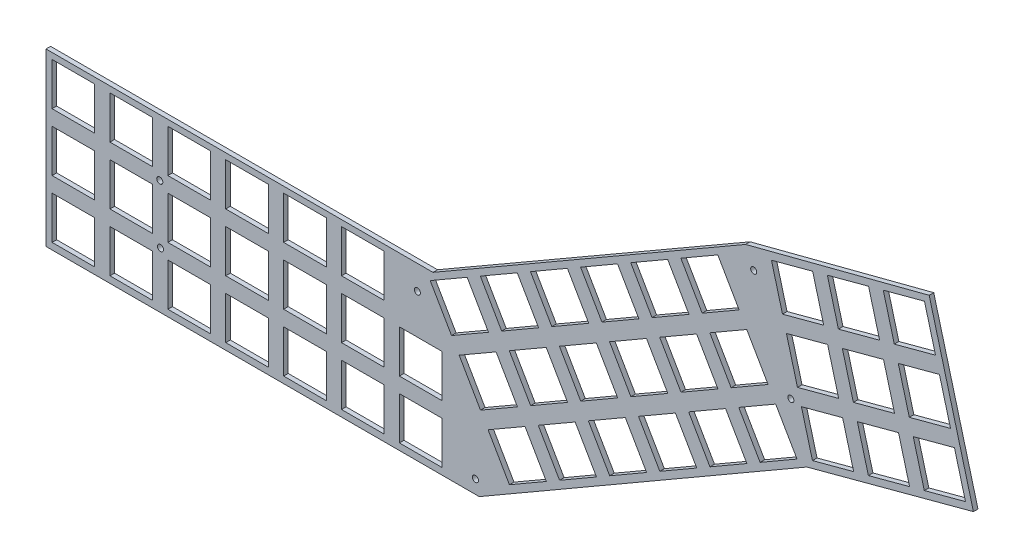
SolidWorks part; units mm, degrees
ref_plane "Plan de face" through (0, 0, 0) normal (0, 0, 1) x (1, 0, 0)
ref_plane "Plan de dessus" through (0, 0, 0) normal (0, 1, 0) x (1, 0, 0)
ref_plane "Plan de droite" through (0, 0, 0) normal (1, 0, 0) x (0, 0, -1)
sketch "Model" plane through (0, 0, 0) normal (0, 0, 1) x (1, 0, 0)
  line L0 (152.8114, 25.9717) -> (138.2826, 80.2215)
  line L1 (98.1506, 11.3316) -> (152.8114, 25.9717)
  line L2 (-9.3986, -50.8585) -> (98.1506, 11.3316)
  line L3 (-151.6088, -50.8585) -> (-9.3986, -50.8585)
  line L4 (-24.5886, 5.3017) -> (-151.6088, 5.2929)
  line L5 (78.0109, 64.5416) -> (-24.5886, 5.3017)
  line L6 (138.2826, 80.2215) -> (78.0109, 64.5416)
  line L7 (-151.6088, 5.3124) -> (-151.6088, -50.8585)
  line L8 (-54.6088, -34.6876) -> (-54.6088, -48.6876)
  line L9 (-54.6088, -48.6876) -> (-40.6088, -48.6876)
  line L10 (-40.6088, -34.6876) -> (-40.6088, -48.6876)
  line L11 (-54.6088, -34.6876) -> (-40.6088, -34.6876)
  line L12 (-35.6088, -34.6876) -> (-35.6088, -48.6876)
  line L13 (-35.6088, -48.6876) -> (-21.6088, -48.6876)
  line L14 (-21.6088, -34.6876) -> (-21.6088, -48.6876)
  line L15 (-35.6088, -34.6876) -> (-21.6088, -34.6876)
  line L16 (-35.6088, -15.6876) -> (-35.6088, -29.6876)
  line L17 (-35.6088, -29.6876) -> (-21.6088, -29.6876)
  line L18 (-21.6088, -15.6876) -> (-21.6088, -29.6876)
  line L19 (-35.6088, -15.6876) -> (-21.6088, -15.6876)
  line L20 (-54.6088, -15.6876) -> (-54.6088, -29.6876)
  line L21 (-54.6088, -29.6876) -> (-40.6088, -29.6876)
  line L22 (-40.6088, -15.6876) -> (-40.6088, -29.6876)
  line L23 (-54.6088, -15.6876) -> (-40.6088, -15.6876)
  line L24 (-54.6088, 3.3124) -> (-54.6088, -10.6876)
  line L25 (-54.6088, -10.6876) -> (-40.6088, -10.6876)
  line L26 (-40.6088, 3.3124) -> (-40.6088, -10.6876)
  line L27 (-54.6088, 3.3124) -> (-40.6088, 3.3124)
  line L28 (-73.6088, -34.6876) -> (-73.6088, -48.6876)
  line L29 (-73.6088, -48.6876) -> (-59.6088, -48.6876)
  line L30 (-59.6088, -34.6876) -> (-59.6088, -48.6876)
  line L31 (-73.6088, -34.6876) -> (-59.6088, -34.6876)
  line L32 (-73.6088, -15.6876) -> (-73.6088, -29.6876)
  line L33 (-73.6088, -29.6876) -> (-59.6088, -29.6876)
  line L34 (-59.6088, -15.6876) -> (-59.6088, -29.6876)
  line L35 (-73.6088, -15.6876) -> (-59.6088, -15.6876)
  line L36 (-73.6088, 3.3124) -> (-73.6088, -10.6876)
  line L37 (-73.6088, -10.6876) -> (-59.6088, -10.6876)
  line L38 (-59.6088, 3.3124) -> (-59.6088, -10.6876)
  line L39 (-73.6088, 3.3124) -> (-59.6088, 3.3124)
  line L40 (-92.6088, -34.6876) -> (-92.6088, -48.6876)
  line L41 (-92.6088, -48.6876) -> (-78.6088, -48.6876)
  line L42 (-78.6088, -34.6876) -> (-78.6088, -48.6876)
  line L43 (-92.6088, -34.6876) -> (-78.6088, -34.6876)
  line L44 (-92.6088, -15.6876) -> (-92.6088, -29.6876)
  line L45 (-92.6088, -29.6876) -> (-78.6088, -29.6876)
  line L46 (-78.6088, -15.6876) -> (-78.6088, -29.6876)
  line L47 (-92.6088, -15.6876) -> (-78.6088, -15.6876)
  line L48 (-92.6088, 3.3124) -> (-92.6088, -10.6876)
  line L49 (-92.6088, -10.6876) -> (-78.6088, -10.6876)
  line L50 (-78.6088, 3.3124) -> (-78.6088, -10.6876)
  line L51 (-92.6088, 3.3124) -> (-78.6088, 3.3124)
  line L52 (-111.6088, -34.6876) -> (-111.6088, -48.6876)
  line L53 (-111.6088, -48.6876) -> (-97.6088, -48.6876)
  line L54 (-97.6088, -34.6876) -> (-97.6088, -48.6876)
  line L55 (-111.6088, -34.6876) -> (-97.6088, -34.6876)
  line L56 (-111.6088, -15.6876) -> (-111.6088, -29.6876)
  line L57 (-111.6088, -29.6876) -> (-97.6088, -29.6876)
  line L58 (-97.6088, -15.6876) -> (-97.6088, -29.6876)
  line L59 (-111.6088, -15.6876) -> (-97.6088, -15.6876)
  line L60 (-130.6088, -34.6876) -> (-130.6088, -48.6876)
  line L61 (-130.6088, -48.6876) -> (-116.6088, -48.6876)
  line L62 (-116.6088, -34.6876) -> (-116.6088, -48.6876)
  line L63 (-130.6088, -34.6876) -> (-116.6088, -34.6876)
  line L64 (-130.6088, -15.6876) -> (-130.6088, -29.6876)
  line L65 (-130.6088, -29.6876) -> (-116.6088, -29.6876)
  line L66 (-116.6088, -15.6876) -> (-116.6088, -29.6876)
  line L67 (-130.6088, -15.6876) -> (-116.6088, -15.6876)
  line L68 (-149.6088, -34.6876) -> (-149.6088, -48.6876)
  line L69 (-149.6088, -48.6876) -> (-135.6088, -48.6876)
  line L70 (-135.6088, -34.6876) -> (-135.6088, -48.6876)
  line L71 (-149.6088, -34.6876) -> (-135.6088, -34.6876)
  line L72 (-149.6088, -15.6876) -> (-149.6088, -29.6876)
  line L73 (-149.6088, -29.6876) -> (-135.6088, -29.6876)
  line L74 (-135.6088, -15.6876) -> (-135.6088, -29.6876)
  line L75 (-149.6088, -15.6876) -> (-135.6088, -15.6876)
  line L76 (-111.6088, 3.3124) -> (-111.6088, -10.6876)
  line L77 (-111.6088, -10.6876) -> (-97.6088, -10.6876)
  line L78 (-97.6088, 3.3124) -> (-97.6088, -10.6876)
  line L79 (-111.6088, 3.3124) -> (-97.6088, 3.3124)
  line L80 (-130.6088, 3.3124) -> (-130.6088, -10.6876)
  line L81 (-130.6088, -10.6876) -> (-116.6088, -10.6876)
  line L82 (-116.6088, 3.3124) -> (-116.6088, -10.6876)
  line L83 (-130.6088, 3.3124) -> (-116.6088, 3.3124)
  line L84 (-149.6088, 3.3124) -> (-149.6088, -10.6876)
  line L85 (-149.6088, -10.6876) -> (-135.6088, -10.6876)
  line L86 (-135.6088, 3.3124) -> (-135.6088, -10.6876)
  line L87 (-149.6088, 3.3124) -> (-135.6088, 3.3124)
  line L88 (96.3487, 27.5969) -> (99.9722, 14.074)
  line L89 (99.9722, 14.074) -> (113.4951, 17.6974)
  line L90 (109.8717, 31.2204) -> (113.4951, 17.6974)
  line L91 (96.3487, 27.5969) -> (109.8717, 31.2204)
  line L92 (91.4311, 45.9495) -> (95.0546, 32.4266)
  line L93 (95.0546, 32.4266) -> (108.5776, 36.05)
  line L94 (104.9541, 49.573) -> (108.5776, 36.05)
  line L95 (91.4311, 45.9495) -> (104.9541, 49.573)
  line L96 (109.7837, 50.8671) -> (113.4072, 37.3441)
  line L97 (113.4072, 37.3441) -> (126.9302, 40.9676)
  line L98 (123.3067, 54.4906) -> (126.9302, 40.9676)
  line L99 (109.7837, 50.8671) -> (123.3067, 54.4906)
  line L100 (114.7013, 32.5145) -> (118.3248, 18.9915)
  line L101 (118.3248, 18.9915) -> (131.8477, 22.615)
  line L102 (128.2243, 36.138) -> (131.8477, 22.615)
  line L103 (114.7013, 32.5145) -> (128.2243, 36.138)
  line L104 (133.0539, 37.4321) -> (136.6774, 23.9091)
  line L105 (136.6774, 23.9091) -> (150.2003, 27.5326)
  line L106 (146.5768, 41.0555) -> (150.2003, 27.5326)
  line L107 (133.0539, 37.4321) -> (146.5768, 41.0555)
  line L108 (128.1363, 55.7847) -> (131.7598, 42.2617)
  line L109 (131.7598, 42.2617) -> (145.2828, 45.8852)
  line L110 (141.6593, 59.4081) -> (145.2828, 45.8852)
  line L111 (128.1363, 55.7847) -> (141.6593, 59.4081)
  line L112 (123.2188, 74.1372) -> (126.8422, 60.6143)
  line L113 (126.8422, 60.6143) -> (140.3652, 64.2378)
  line L114 (136.7417, 77.7607) -> (140.3652, 64.2378)
  line L115 (123.2188, 74.1372) -> (136.7417, 77.7607)
  line L116 (104.8662, 69.2197) -> (108.4896, 55.6967)
  line L117 (108.4896, 55.6967) -> (122.0126, 59.3202)
  line L118 (118.3891, 72.8432) -> (122.0126, 59.3202)
  line L119 (104.8662, 69.2197) -> (118.3891, 72.8432)
  line L120 (86.5136, 64.3021) -> (90.137, 50.7792)
  line L121 (90.137, 50.7792) -> (103.66, 54.4026)
  line L122 (100.0365, 67.9256) -> (103.66, 54.4026)
  line L123 (86.5136, 64.3021) -> (100.0365, 67.9256)
  line L124 (87.902, 24.0982) -> (94.902, 11.9739)
  line L125 (94.902, 11.9739) -> (82.7777, 4.9739)
  line L126 (75.7777, 17.0982) -> (82.7777, 4.9739)
  line L127 (87.902, 24.0982) -> (75.7777, 17.0982)
  line L128 (78.402, 40.5527) -> (85.402, 28.4283)
  line L129 (85.402, 28.4283) -> (73.2777, 21.4283)
  line L130 (66.2777, 33.5527) -> (73.2777, 21.4283)
  line L131 (78.402, 40.5527) -> (66.2777, 33.5527)
  line L132 (68.902, 57.0072) -> (75.902, 44.8828)
  line L133 (75.902, 44.8828) -> (63.7777, 37.8828)
  line L134 (56.7777, 50.0072) -> (63.7777, 37.8828)
  line L135 (68.902, 57.0072) -> (56.7777, 50.0072)
  line L136 (71.4475, 14.5982) -> (78.4475, 2.4739)
  line L137 (78.4475, 2.4739) -> (66.3232, -4.5261)
  line L138 (59.3232, 7.5982) -> (66.3232, -4.5261)
  line L139 (71.4475, 14.5982) -> (59.3232, 7.5982)
  line L140 (61.9475, 31.0527) -> (68.9475, 18.9283)
  line L141 (68.9475, 18.9283) -> (56.8232, 11.9283)
  line L142 (49.8232, 24.0527) -> (56.8232, 11.9283)
  line L143 (61.9475, 31.0527) -> (49.8232, 24.0527)
  line L144 (52.4475, 47.5072) -> (59.4475, 35.3828)
  line L145 (59.4475, 35.3828) -> (47.3232, 28.3828)
  line L146 (40.3232, 40.5072) -> (47.3232, 28.3828)
  line L147 (52.4475, 47.5072) -> (40.3232, 40.5072)
  line L148 (54.9931, 5.0982) -> (61.9931, -7.0261)
  line L149 (61.9931, -7.0261) -> (49.8687, -14.0261)
  line L150 (42.8687, -1.9018) -> (49.8687, -14.0261)
  line L151 (54.9931, 5.0982) -> (42.8687, -1.9018)
  line L152 (45.4931, 21.5527) -> (52.4931, 9.4283)
  line L153 (52.4931, 9.4283) -> (40.3687, 2.4283)
  line L154 (33.3687, 14.5527) -> (40.3687, 2.4283)
  line L155 (45.4931, 21.5527) -> (33.3687, 14.5527)
  line L156 (38.5386, -4.4018) -> (45.5386, -16.5261)
  line L157 (45.5386, -16.5261) -> (33.4142, -23.5261)
  line L158 (26.4142, -11.4018) -> (33.4142, -23.5261)
  line L159 (38.5386, -4.4018) -> (26.4142, -11.4018)
  line L160 (29.0386, 12.0527) -> (36.0386, -0.0717)
  line L161 (36.0386, -0.0717) -> (23.9142, -7.0717)
  line L162 (16.9142, 5.0527) -> (23.9142, -7.0717)
  line L163 (29.0386, 12.0527) -> (16.9142, 5.0527)
  line L164 (35.9931, 38.0072) -> (42.9931, 25.8828)
  line L165 (42.9931, 25.8828) -> (30.8687, 18.8828)
  line L166 (23.8687, 31.0072) -> (30.8687, 18.8828)
  line L167 (35.9931, 38.0072) -> (23.8687, 31.0072)
  line L168 (19.5386, 28.5072) -> (26.5386, 16.3828)
  line L169 (26.5386, 16.3828) -> (14.4142, 9.3828)
  line L170 (7.4142, 21.5072) -> (14.4142, 9.3828)
  line L171 (19.5386, 28.5072) -> (7.4142, 21.5072)
  line L172 (3.0841, 19.0072) -> (10.0841, 6.8828)
  line L173 (10.0841, 6.8828) -> (-2.0403, -0.1172)
  line L174 (-9.0403, 12.0072) -> (-2.0403, -0.1172)
  line L175 (3.0841, 19.0072) -> (-9.0403, 12.0072)
  line L176 (12.5841, 2.5527) -> (19.5841, -9.5717)
  line L177 (19.5841, -9.5717) -> (7.4597, -16.5717)
  line L178 (0.4597, -4.4473) -> (7.4597, -16.5717)
  line L179 (12.5841, 2.5527) -> (0.4597, -4.4473)
  line L180 (22.0841, -13.9018) -> (29.0841, -26.0261)
  line L181 (29.0841, -26.0261) -> (16.9597, -33.0261)
  line L182 (9.9597, -20.9018) -> (16.9597, -33.0261)
  line L183 (22.0841, -13.9018) -> (9.9597, -20.9018)
  line L184 (5.6296, -23.4018) -> (12.6296, -35.5261)
  line L185 (12.6296, -35.5261) -> (0.5053, -42.5261)
  line L186 (-6.4947, -30.4018) -> (0.5053, -42.5261)
  line L187 (5.6296, -23.4018) -> (-6.4947, -30.4018)
  line L188 (-3.8704, -6.9473) -> (3.1296, -19.0717)
  line L189 (3.1296, -19.0717) -> (-8.9947, -26.0717)
  line L190 (-15.9947, -13.9473) -> (-8.9947, -26.0717)
  line L191 (-3.8704, -6.9473) -> (-15.9947, -13.9473)
  line L192 (-13.3704, 9.5072) -> (-25.4947, 2.5072)
  line L193 (-25.4947, 2.5072) -> (-18.4947, -9.6172)
  line L194 (-6.3704, -2.6172) -> (-18.4947, -9.6172)
  line L195 (-13.3704, 9.5072) -> (-6.3704, -2.6172)
  circle A0 centre (80.6856, 58.4893) radius 1
  circle A1 centre (92.8776, 28.0855) radius 1
  circle A2 centre (-29.7028, -2.6485) radius 1
  circle A3 centre (-10.6528, -46.4381) radius 1
  circle A4 centre (-114.2594, -13.4181) radius 1
  circle A5 centre (-114.0308, -32.4935) radius 1
extrude "Boss.-Extru.1" add sketch "Model" along normal blind 1.5 contours L4 L7 L3 L2 L1 L0 L6 L5 A5 A4 A3 A2 A1 A0 L191 L188 L189 L190 L187 L184 L185 L186 L183 L180 L181 L182 L179 L176 L177 L178 L175 L172 L173 L174 L171 L168 L169 L170 region at (1.4905, 1.6477, 0)
